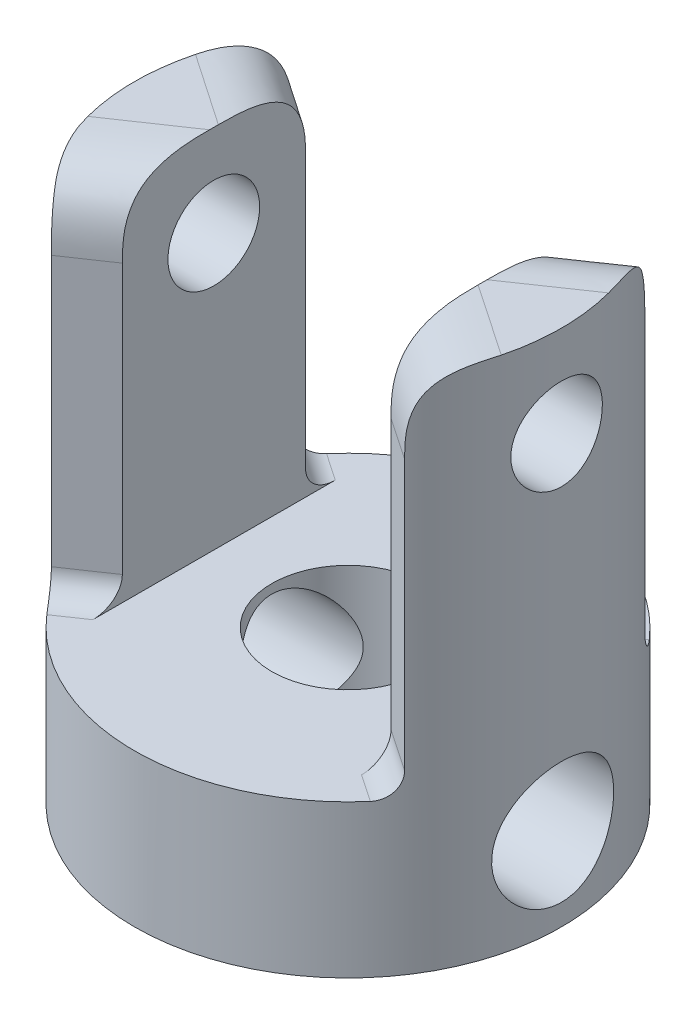
SolidWorks part; units mm, degrees
ref_plane "Front Plane" through (0, 0, 0) normal (0, 0, 1) x (1, 0, 0)
ref_plane "Top Plane" through (0, 0, 0) normal (0, 1, 0) x (1, 0, 0)
ref_plane "Right Plane" through (0, 0, 0) normal (1, 0, 0) x (0, 0, -1)
sketch "Sketch1" plane through (0, 0, 0) normal (0, 1, 0) x (1, 0, 0)
  circle A0 centre (0, 0) radius 3.5
  circle A1 centre (0, 0) radius 1.25
  dimension "D1" = 7
  dimension "D2" = 2.5
extrude "Boss-Extrude1" add sketch "Sketch1" along normal blind 2.5
sketch "Sketch2" plane through (0, 2.5, 0) normal (0, 1, 0) x (1, 0, 0)
  line L0 (-2.2023, -1.4967) -> (-2.8948, -1.9673)
  line L6 (2.8888, 1.976) -> (2.2023, 1.5064)
  line L7 (2.2023, 1.5064) -> (2.2023, -1.4967)
  line L8 (2.2023, -1.4967) -> (2.8948, -1.9673)
  line L9 (0, 0) -> (0, 2.7659)
  line L10 (-2.2, 0.0033) -> (-2.2023, -1.4967)
  line L12 (0, 0) -> (-2.2, 0.0033) construction
  line L13 (-2.2, 0.0033) -> (-2.1977, 1.5033)
  line L14 (-2.1977, 1.5033) -> (-2.8888, 1.976)
  arc A2 (2.8888, 1.976) -> (2.8948, -1.9673) centre (0, 0) cw
  arc A3 (-2.8888, 1.976) -> (-2.8948, -1.9673) centre (0, 0) ccw
  circle A4 centre (0, 0) radius 3.5 construction
  dimension "D1" = 1.5
  dimension "D2" = 2.2
extrude "Boss-Extrude2" add sketch "Sketch2" along normal blind 6
fillet "Fillet5" radius 1.18 4 edges at (-2.5485, 8.5, 1.732) (2.5485, 8.5, 1.732) (2.5455, 8.5, -1.7412) (-2.5433, 8.5, -1.7397)
sketch "Sketch4" plane through (0, 0, 0) normal (1, 0, 0) x (0, 0, -1)
  line L0 (0, 0) -> (0, 1.35)
  circle A0 centre (0, 1.35) radius 1
  dimension "D1" = 2
  dimension "D2" = 1.35
extrude "Cut-Extrude1" cut sketch "Sketch4" against normal through all both and the other way through all contours A0
sketch "Sketch5" plane through (0, 0, 0) normal (1, 0, 0) x (0, 0, -1)
  line L0 (0, 0) -> (0, 7)
  line L1 (0.8864, 8.5) -> (-0.8762, 8.5) construction
  circle A1 centre (0, 7) radius 0.75
  dimension "D1" = 1.5
  dimension "D2" = 1.5
extrude "Cut-Extrude2" cut sketch "Sketch5" against normal through all both and the other way through all
fillet "Fillet6" radius 0.4 4 edges at (-2.5433, 2.5, -1.7397) (-2.5485, 2.5, 1.732) (2.5485, 2.5, 1.732) (2.5455, 2.5, -1.7412)
